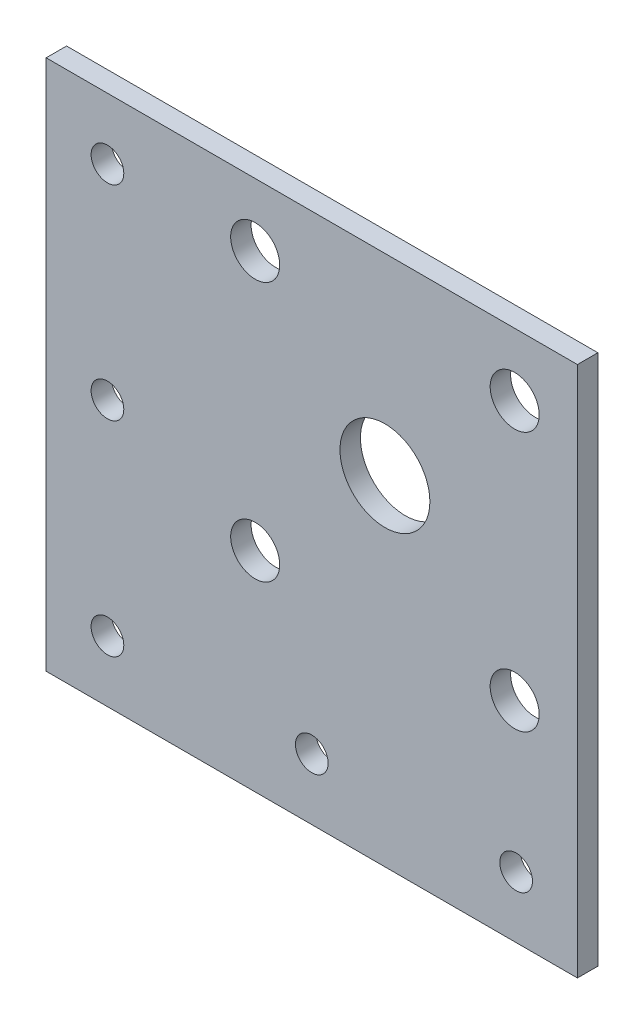
SolidWorks part; units mm, degrees
ref_plane "前视基准面" through (0, 0, 0) normal (0, 0, 1) x (1, 0, 0)
ref_plane "上视基准面" through (0, 0, 0) normal (0, 1, 0) x (1, 0, 0)
ref_plane "右视基准面" through (0, 0, 0) normal (1, 0, 0) x (0, 0, -1)
sketch "草图1" plane through (0, 0, 0) normal (0, 0, 1) x (1, 0, 0)
  line L0 (-82.9, -17.9) -> (-42.9, -17.9) construction
  line L3 (-42.9, -32.9) -> (-42.9, 32.9) construction
  line L4 (-82.9, 1957.1) -> (-82.9, -82.9) construction
  line L5 (-82.9, 47.1) -> (-82.9, -82.9)
  line L6 (-67.9, 47.1) -> (-67.9, -82.9) construction
  line L7 (-82.9, -82.9) -> (47.1, -82.9)
  line L8 (-82.9, -82.9) -> (-82.9, 47.1)
  line L9 (-82.9, 47.1) -> (47.1, 47.1)
  line L10 (47.1, -82.9) -> (47.1, 47.1)
  line L11 (-42.9, -67.9) -> (57.1, -67.9) construction
  line L13 (7.1, -67.9) -> (7.1, -50.9) construction
  line L14 (637.1, -50.9) -> (-42.9, -50.9) construction
  line L15 (31.75, -31.75) -> (-31.75, -31.75) construction
  line L16 (31.75, -31.75) -> (31.75, 31.75) construction
  line L17 (31.75, 31.75) -> (-31.75, 31.75) construction
  line L18 (-31.75, -31.75) -> (-31.75, 31.75) construction
  line L19 (31.75, -31.75) -> (-31.75, 31.75) construction
  line L20 (31.75, 31.75) -> (-31.75, -31.75) construction
  circle A1 centre (-31.75, -31.75) radius 6
  circle A3 centre (-31.75, 31.75) radius 6
  circle A5 centre (31.75, 31.75) radius 6
  circle A7 centre (31.75, -31.75) radius 6
  circle A8 centre (-67.9, 32.1) radius 4
  circle A9 centre (-67.9, -17.9) radius 4
  circle A10 centre (-67.9, -67.9) radius 4
  circle A11 centre (-17.9, -67.9) radius 4
  circle A12 centre (32.1, -67.9) radius 4
  circle A13 centre (0, 0) radius 11
  dimension "D5" = 8
  dimension "D6" = 8
  dimension "D7" = 15
  dimension "D9" = 22
  dimension "D11" = 12
  dimension "D1" = 130
  dimension "D2" = 130
  dimension "D3" = 15
  dimension "D4" = 50
  dimension "D8" = 50
  dimension "D10" = 63.5
extrude "凸台-拉伸1" add sketch "草图1" along normal blind 5 contours L7 L10 L9 L5 A12 A11 A1 A3 A5 A7 A8 A9 A10 region at (-18.5244, -18.5244, 0)
